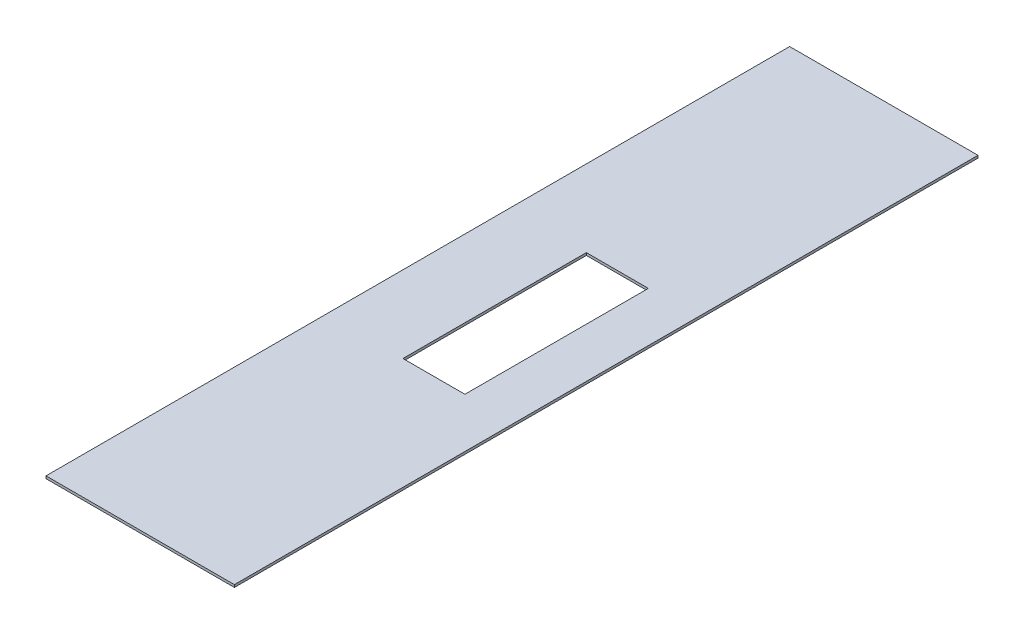
SolidWorks part; units mm, degrees
ref_plane "Ebene vorne" through (0, 0, 0) normal (0, 0, 1) x (1, 0, 0)
ref_plane "Ebene oben" through (0, 0, 0) normal (0, 1, 0) x (1, 0, 0)
ref_plane "Ebene rechts" through (0, 0, 0) normal (1, 0, 0) x (0, 0, -1)
sketch "Skizze1" plane through (0, 0, 0) normal (0, 0, 1) x (1, 0, 0)
  line L0 (0, 0) -> (76, 0)
  dimension "D1" = 76
extrude "Linear-Austragen-Dünn1" add sketch "Skizze1" along normal blind 300 thin thin type one direction wall 1
sketch "Skizze2" plane through (0, -1, 0) normal (0, -1, 0) x (1, 0, 0)
  line L0 (56, 113) -> (56, 0) construction
  line L1 (56, 187) -> (31, 187)
  line L2 (56, 187) -> (56, 113)
  line L3 (56, 113) -> (31, 113)
  line L4 (31, 187) -> (31, 113)
  line L5 (0, 0) -> (76, 0) construction
  line L6 (56, 187) -> (56, 300) construction
  line L7 (0, 300) -> (76, 300) construction
  line L8 (56, 187) -> (76, 187) construction
  line L9 (76, 300) -> (76, 0) construction
  line L10 (31, 187) -> (0, 187) construction
  line L11 (0, 300) -> (0, 0) construction
  dimension "D1" = 25
  dimension "D2" = 20
  dimension "D3" = 74
extrude "Schnitt-Linear austragen1" cut sketch "Skizze2" against normal blind 10
